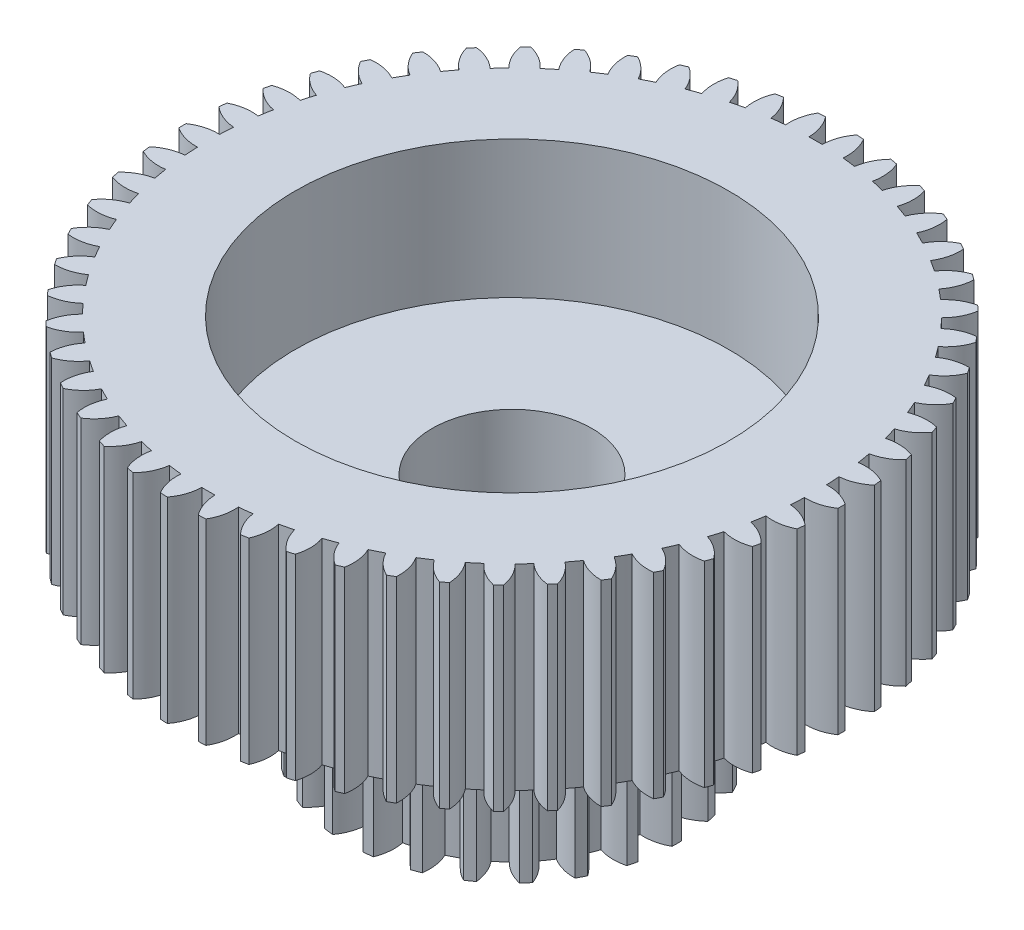
SolidWorks part; units mm, degrees
ref_plane "Ebene vorne" through (0, 0, 0) normal (0, 0, 1) x (1, 0, 0)
ref_plane "Ebene oben" through (0, 0, 0) normal (0, 1, 0) x (1, 0, 0)
ref_plane "Ebene rechts" through (0, 0, 0) normal (1, 0, 0) x (0, 0, -1)
sketch "Skizze1" plane through (0, 0, 0) normal (0, 1, 0) x (1, 0, 0)
  circle A0 centre (0, 0) radius 8.4
  circle A1 centre (0, 0) radius 4.075
  dimension "D2" = 8.15
  dimension "D1" = 16.8
extrude "Aufsatz-Linear austragen1" add sketch "Skizze1" along normal blind 9.1
sketch "Skizze2" plane through (0, 9.1, 0) normal (0, 1, 0) x (1, 0, 0)
  circle A0 centre (0, 0) radius 16.8
  circle A1 centre (0, 0) radius 4.075
  dimension "D1" = 33.6
  dimension "D2" = 8.15
extrude "Aufsatz-Linear austragen2" add sketch "Skizze2" along normal blind 10
sketch "Skizze3" plane through (0, 19.1, 0) normal (0, 1, 0) x (1, 0, 0)
  circle A0 centre (0, 0) radius 11.05
  dimension "D1" = 22.1
extrude "Schnitt-Linear austragen1" cut sketch "Skizze3" against normal blind 7
sketch "Skizze5" plane through (0, 19.1, 0) normal (0, 1, 0) x (1, 0, 0)
  line L0 (0, 0) -> (0, 16.8) construction
  line L1 (0, 0) -> (-0.3367, 15.4763) construction
  line L2 (0, 0) -> (0.9768, 16.7716) construction
  line L3 (-0.4712, 16.1931) -> (0.4712, 16.1931) construction
  line L4 (0.4712, 16.1931) -> (1.4119, 16.1384) construction
  line L5 (0, 14.8986) -> (-0.6869, 16.786) construction
  circle A0 centre (0, 0) radius 16.8
  circle A1 centre (0, 0) radius 16.2 construction
  circle A2 centre (0, 0) radius 15.48
  arc A3 (-0.792, 16.7813) -> (-0.3367, 15.4763) centre (-2.5744, 15.4277) cw
  arc A4 (0.792, 16.7813) -> (0.3367, 15.4763) centre (2.5744, 15.4277) ccw
  dimension "D1" = 33.6
  dimension "D2" = 32.4
  dimension "D3" = 30.96
  dimension "D4" = 3.333
  dimension "D5" = 20
extrude "Schnitt-Linear austragen2" cut sketch "Skizze5" against normal up to surface (10 mm away) contours A4 A0 A3 A2 region at (0, 19.1, -16.2378) up to face at (0, 9.1, 8.4)
pattern_circular "Kreismuster1" count 54 over 360 about axis through (0, 12.1, 0) along (0, 1, 0) of "Schnitt-Linear austragen2"
sketch "Skizze6" plane through (0, 0, 0) normal (0, -1, 0) x (1, 0, 0)
  line L0 (0, 0) -> (0, 8.4) construction
  line L1 (0, 0) -> (-0.328, 7.0724) construction
  line L2 (0, 0) -> (1.0125, 8.3388) construction
  line L3 (-0.471, 7.7858) -> (0.471, 7.7858) construction
  line L4 (0.471, 7.7858) -> (1.406, 7.6722) construction
  line L5 (0, 6.4918) -> (-0.6844, 8.3721) construction
  circle A0 centre (0, 0) radius 8.4
  circle A1 centre (0, 0) radius 7.8 construction
  circle A2 centre (0, 0) radius 7.08
  arc A3 (-0.7757, 8.3641) -> (-0.328, 7.0724) centre (-2.7381, 6.9606) cw
  arc A4 (0.7757, 8.3641) -> (0.328, 7.0724) centre (2.7381, 6.9606) ccw
  dimension "D1" = 16.8
  dimension "D5" = 20
  dimension "D2" = 15.6
  dimension "D3" = 14.16
  dimension "D4" = 6.923
extrude "Schnitt-Linear austragen3" cut sketch "Skizze6" against normal up to surface (9.1 mm away) contours A4 A0 A3 A2 region at (0, 0, 7.8346) up to face at (0, 9.1, 8.4)
pattern_circular "Kreismuster2" count 26 over 360 about axis through (0, 9.1, 0) along (0, -1, 0) of "Schnitt-Linear austragen3" reverse direction yes
equation "\"Tooth1\" = 54"
equation "\"Tooth2\" = 26"
equation "\"Module\"= 0.6mm"
equation "\"D1@Skizze2\"=(\"Tooth1\"+2)*\"Module\""
equation "\"D1@Skizze1\"=(\"Tooth2\"+2)*\"Module\""
equation "\"D1@Skizze5\"=(\"Tooth1\"+2)*\"Module\""
equation "\"D2@Skizze5\"=\"Tooth1\"*\"Module\""
equation "\"D3@Skizze5\"=(\"Module\"*\"Tooth1\"- (\"Module\"*if(\"Module\" => 1.25,2.25,2.4)))"
equation "\"D4@Skizze5\"=180/\"Tooth1\""
equation "\"D1@Kreismuster1\"=\"Tooth1\""
equation "\"D3@Skizze6\"=(\"Module\"*\"Tooth2\"- (\"Module\"*if(\"Module\" => 1.25,2.25,2.4)))"
equation "\"D2@Skizze6\"=\"Tooth2\"*\"Module\""
equation "\"D1@Skizze6\"=(\"Tooth2\"+2)*\"Module\""
equation "\"D4@Skizze6\"=180/\"Tooth2\""
equation "\"D1@Kreismuster2\"=\"Tooth2\""
